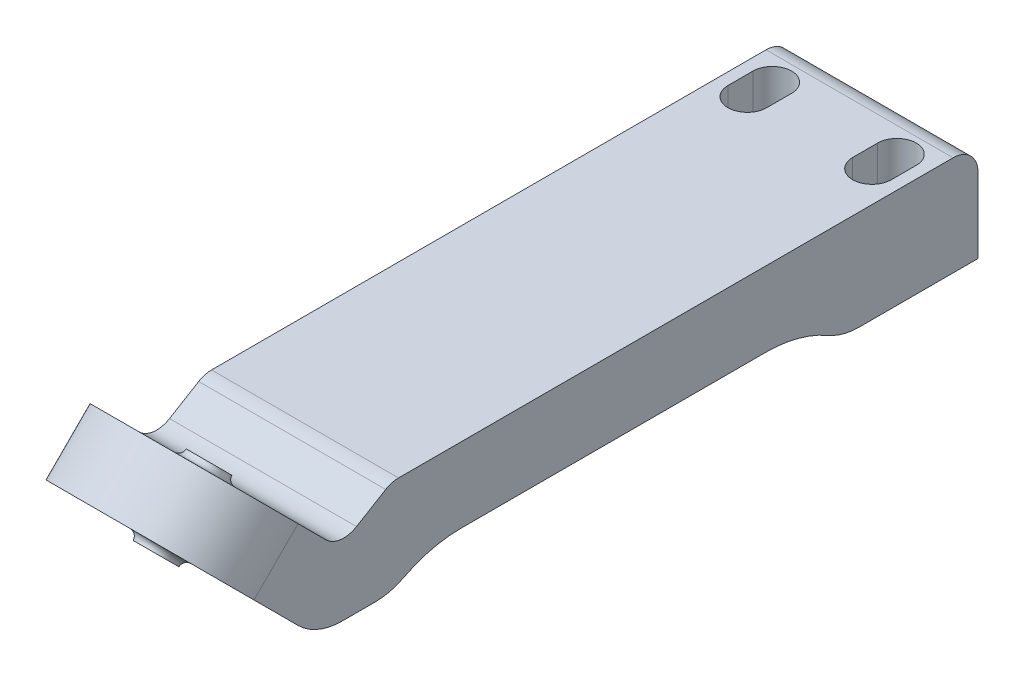
SolidWorks part; units mm, degrees
ref_plane "前视基准面" through (0, 0, 0) normal (0, 0, 1) x (1, 0, 0)
ref_plane "上视基准面" through (0, 0, 0) normal (0, 1, 0) x (1, 0, 0)
ref_plane "右视基准面" through (0, 0, 0) normal (1, 0, 0) x (0, 0, -1)
other "Configuration Table"
sketch "草图10" plane through (0, 0, 0) normal (0, 0, 1) x (1, 0, 0)
  line L0 (-7.5, 20.6821) -> (7.5, 20.6821) construction
  line L1 (-7.5, 20.6821) -> (7.5, 20.6821)
  line L2 (7.5, 20.6821) -> (7.5, 28.6821)
  line L3 (7.5, 28.6821) -> (-7.5, 28.6821)
  line L4 (-7.5, 28.6821) -> (-7.5, 20.6821)
  arc A0 (-7.5, 20.6821) -> (7.5, 20.6821) centre (0, 0) ccw construction
  dimension "D1" = 44
  dimension "D2" = 15
  dimension "D3" = 8
extrude "凸台-拉伸7" add sketch "草图10" along normal blind 41
sketch "草图11" plane through (0, 28.6821, 0) normal (0, 1, 0) x (1, 0, 0)
  line L0 (0, 3.3102) -> (0, -13.8287) construction
  line L1 (-5, -4) -> (-5, -6) construction
  line L2 (-3.45, -4) -> (-3.45, -6)
  line L3 (-6.55, -4) -> (-6.55, -6)
  line L5 (5, -4) -> (5, -6) construction
  line L6 (3.45, -4) -> (3.45, -6)
  line L7 (6.55, -4) -> (6.55, -6)
  line L8 (7.5, 0) -> (-7.5, 0) construction
  arc A0 (-3.45, -4) -> (-6.55, -4) centre (-5, -4) ccw
  arc A1 (-6.55, -6) -> (-3.45, -6) centre (-5, -6) ccw
  arc A2 (3.45, -4) -> (6.55, -4) centre (5, -4) cw
  arc A3 (6.55, -6) -> (3.45, -6) centre (5, -6) cw
  point P5 (-5, -5)
  point P14 (5, -5)
  dimension "D2" = 1.55
  dimension "D1" = 5
  dimension "D3" = 2
  dimension "D4" = 10
extrude "切除-拉伸4" cut sketch "草图11" against normal blind 11
sketch "草图12" plane through (0, 0, 41) normal (0, 0, 1) x (1, 0, 0)
  line L0 (7.5, 20.6821) -> (7.5, 28.6821) construction
  line L1 (-7.5, 28.6821) -> (7.5, 28.6821)
  line L2 (-7.5, 28.6821) -> (-7.5, 22.6821)
  line L3 (-7.5, 22.6821) -> (7.5, 22.6821)
  line L4 (7.5, 28.6821) -> (7.5, 22.6821)
  dimension "D1" = 6
extrude "凸台-拉伸8" add sketch "草图12" along normal blind 6
sketch "草图14" plane through (0, 0, 47) normal (0, 0, 1) x (1, 0, 0)
  line L0 (-7.5, 20.6821) -> (7.5, 20.6821) construction
  line L1 (0, 26) -> (-20.4245, 26) construction
  line L2 (-7.5, 26) -> (7.5, 26)
  line L3 (7.5, 26) -> (7.5, 21)
  line L4 (7.5, 20.6821) -> (7.5, 22.6821) construction
  line L5 (7.5, 21) -> (-7.5, 21)
  line L6 (-7.5, 22.6821) -> (-7.5, 20.6821) construction
  line L7 (-7.5, 21) -> (-7.5, 26)
  line L8 (-7.5, 28.6821) -> (-7.5, 22.6821) construction
  arc A0 (-7.5, 20.6821) -> (7.5, 20.6821) centre (0, 0) ccw construction
  circle A1 centre (0, 0) radius 26 construction
  dimension "D1" = 52
  dimension "D2" = 5
extrude "凸台-拉伸9" add sketch "草图14" along normal blind 4
sketch "草图17" plane through (-7.5, 0, 0) normal (-1, 0, 0) x (0, 0, 1)
  line L0 (51, 26) -> (54.5355, 29.5355)
  line L1 (51, 26) -> (47, 26) construction
  line L2 (58.0711, 26) -> (53.0711, 21)
  line L4 (54.5355, 29.5355) -> (58.0711, 26)
  line L5 (51, 26) -> (51, 21)
  line L6 (51, 21) -> (53.0711, 21)
  dimension "D1" = 135
  dimension "D2" = 5
  dimension "D3" = 5
extrude "凸台-拉伸10" add sketch "草图17" against normal blind 15
sketch "草图18" plane through (0, -16.0355, 16.0355) normal (0, -0.7071, 0.7071) x (1, 0, 0)
  line L0 (7.5, 59.4472) -> (-7.5, 59.4472) construction
  line L1 (7.5, 52.3762) -> (7.5, 59.4472) construction
  line L2 (7.5, 59.4472) -> (-7.5, 59.4472)
  arc A0 (-7.5, 59.4472) -> (7.5, 59.4472) centre (0, 59.4472) cw
extrude "凸台-拉伸11" add sketch "草图18" against normal blind 5
sketch "草图19" plane through (0, -16.0355, 16.0355) normal (0, -0.7071, 0.7071) x (1, 0, 0)
  circle A0 centre (0, 59.4472) radius 1.1
  dimension "D1" = 2.2
extrude "切除-拉伸5" cut sketch "草图19" against normal blind 5
sketch "草图20" plane through (0, -16.0355, 16.0355) normal (0, -0.7071, 0.7071) x (1, 0, 0)
  circle A0 centre (0, 59.4472) radius 1.1 construction
  circle A1 centre (0, 59.4472) radius 1.1
  circle A2 centre (0, 59.4472) radius 1.5
  dimension "D1" = 3
extrude "凸台-拉伸12" add sketch "草图20" along normal blind 0.5
sketch "草图21" plane through (0, -12.5, 12.5) normal (0, 0.7071, -0.7071) x (1, 0, 0)
  circle A0 centre (0, -59.4472) radius 1.1 construction
  circle A1 centre (0, -59.4472) radius 1.1
  circle A2 centre (0, -59.4472) radius 1.5
  dimension "D1" = 3
extrude "凸台-拉伸13" add sketch "草图21" along normal blind 0.5
fillet "圆角4" radius 0.5 2 edges at (0, 24.9393, 57.0104) (0, 30.5962, 55.5962)
chamfer "倒角1" distance 2.7 angle 59 1 edges at (0, 26, 47) first distance on face at (0, 27.3411, 47)
fillet "圆角7" radius 2 2 edges at (0, 28.6821, 47.0298) (0, 26.1852, 51.1852)
sketch "草图23" plane through (0, 0, 41) normal (0, 0, 1) x (1, 0, 0)
  line L4 (7.5, 22.6821) -> (-7.5, 22.6821)
  line L5 (-7.5, 22.6821) -> (-7.5, 20.6821)
  line L6 (-7.5, 20.6821) -> (7.5, 20.6821)
  line L7 (7.5, 20.6821) -> (7.5, 22.6821)
  line L8 (7.5, 22.6821) -> (-7.5, 22.6821)
  line L9 (-7.5, 22.6821) -> (-7.5, 20.6821)
  line L10 (-7.5, 20.6821) -> (7.5, 20.6821)
  line L11 (7.5, 20.6821) -> (7.5, 22.6821)
  dimension "D1" = 0
extrude "切除-拉伸6" cut sketch "草图23" against normal blind 30
fillet "圆角8" radius 10 2 edges at (0, 22.6821, 11) (0, 22.6821, 47)
fillet "圆角9" radius 5 3 edges at (0, 20.6821, 11) (0, 21, 47) (0, 21, 53.0711)
fillet "圆角10" radius 2 1 edges at (0, 28.6821, 0)
